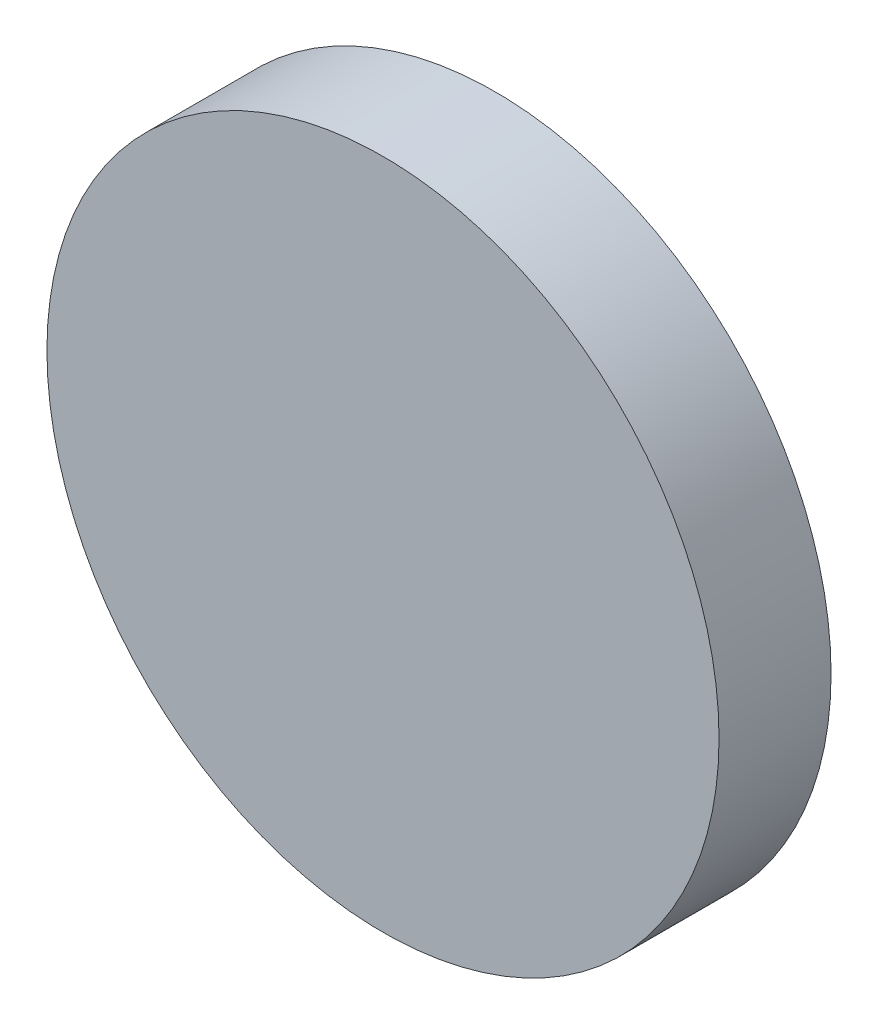
SolidWorks part; units mm, degrees
ref_plane "Piano frontale" through (0, 0, 0) normal (0, 0, 1) x (1, 0, 0)
ref_plane "Piano superiore" through (0, 0, 0) normal (0, 1, 0) x (1, 0, 0)
ref_plane "Piano destro" through (0, 0, 0) normal (1, 0, 0) x (0, 0, -1)
sketch "Schizzo1" plane through (0, 0, 0) normal (0, 0, 1) x (1, 0, 0)
  circle A0 centre (0, 0) radius 150
extrude "Estrusione-Estrusione1" add sketch "Schizzo1" against normal blind 50
